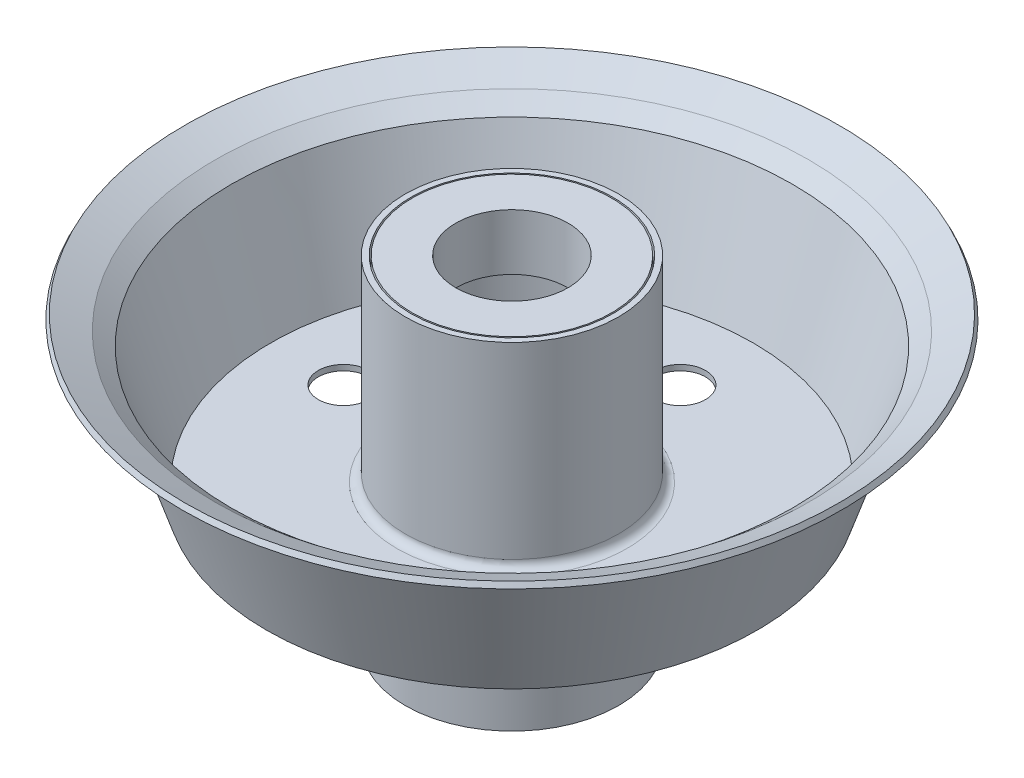
SolidWorks part; units mm, degrees
note: The reader was unsure of these and kept them because the rebuilt part matched: shared geometry of "Эскиз4<2>".
ref_plane "Спереди" through (0, 0, 0) normal (0, 0, 1) x (1, 0, 0)
ref_plane "Сверху" through (0, 0, 0) normal (0, 1, 0) x (1, 0, 0)
ref_plane "Справа" through (0, 0, 0) normal (1, 0, 0) x (0, 0, -1)
sketch "Эскиз1" plane through (0, 0, 0) normal (0, 0, 1) x (1, 0, 0)
  line L0 (0, 0) -> (0, -32.1034) construction
  line L1 (-5.6001, 0) -> (69.589, 0) construction
  line L2 (19, 0) -> (43, 0)
  line L3 (52.8896, 23.3322) -> (58.3028, 25.953)
  line L4 (50, 21) -> (43, 0)
  line L5 (50, 21) -> (52.8896, 23.3322)
  point P11 (43.073, -0.6031)
revolve "Повернуть-Тонкостенный1" add sketch "Эскиз1" angle 360 about L0
sketch "Эскиз2" plane through (0, 0, 0) normal (0, 1, 0) x (1, 0, 0)
  line L0 (-12.04, 0) -> (79.8729, 0) construction
  line L1 (0, 1.1092) -> (0, -37.1354) construction
  line L2 (19, 0) -> (19, -28.0145) construction
  line L3 (0, 19) -> (26.2597, 19) construction
  circle A0 centre (30, 0) radius 4.5
  circle A1 centre (-30, 0) radius 4.5
  circle A3 centre (0, 30) radius 4.5
  circle A4 centre (0, -30) radius 4.5
  dimension "D1" = 11
  dimension "D2" = 11
  dimension "D3" = 9
  dimension "D4" = 9
  dimension "D5" = 30
extrude "Вытянуть1" cut sketch "Эскиз2" against normal mid plane 80
sketch "Эскиз3" plane through (0, 0, 0) normal (0, 1, 0) x (1, 0, 0)
  circle A0 centre (0, 0) radius 19
  circle A1 centre (0, 0) radius 18
  dimension "D1" = 36
  dimension "D2" = 38
extrude "Вытянуть10" add sketch "Эскиз3" against normal blind 25 and the other way blind 35
fillet "Скругление2" radius 1.5 1 edges at (0, 0, 19)
sketch "Эскиз4" plane through (0, 0, 0) normal (0, 1, 0) x (1, 0, 0)
  circle A0 centre (0, 0) radius 17.75
  circle A1 centre (0, 0) radius 10
  dimension "D1" = 20
  dimension "D2" = 35.5
extrude "Вытянуть11" add sketch "Эскиз4" along normal blind 10 from offset 25
extrude "Вытянуть12" add sketch "Эскиз4<2>" against normal blind 10 from offset 15 separate body
sketch "Эскиз4<2>" plane through (0, 0, 0) normal (0, 1, 0) x (1, 0, 0) same geometry as "Эскиз4"
sketch "Эскиз6" plane through (0, 0, 0) normal (0, 1, 0) x (1, 0, 0)
  line L0 (0, 0) -> (-80.9746, 0) construction
  line L1 (0, 0) -> (0, 61.8523) construction
  circle A0 centre (0, 0) radius 30 construction
  circle A1 centre (-22.3607, 20) radius 3
  circle A2 centre (22.3607, -20) radius 3
  point P15 (-26.8342, 25.339)
  point P26 (-2.7542, 23.1356)
  dimension "D1" = 20
  dimension "D3" = 6
  dimension "D4" = 6
  dimension "D2" = 20
extrude "Вытянуть13" cut sketch "Эскиз6" against normal mid plane 30
